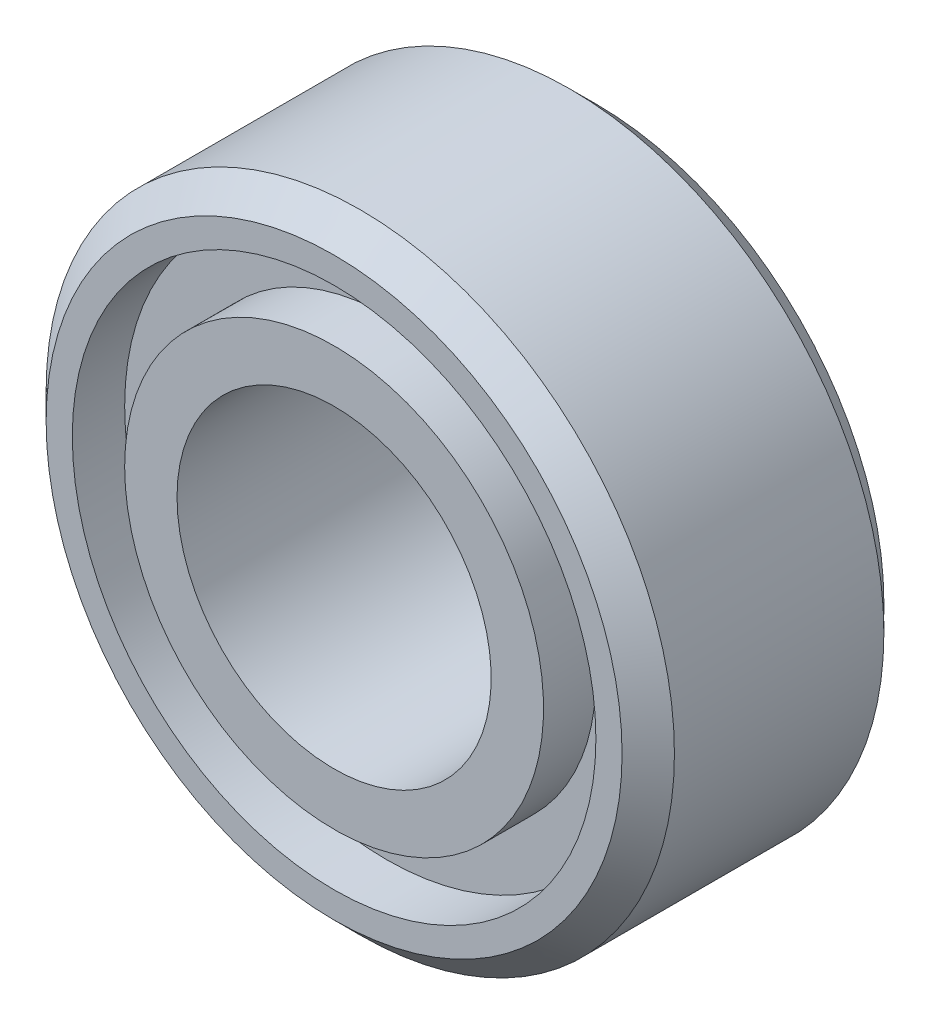
SolidWorks part; units mm, degrees
ref_plane "Front Plane" through (0, 0, 0) normal (0, 0, 1) x (1, 0, 0)
ref_plane "Top Plane" through (0, 0, 0) normal (0, 1, 0) x (1, 0, 0)
ref_plane "Right Plane" through (0, 0, 0) normal (1, 0, 0) x (0, 0, -1)
ref_plane "Plane1" through (0, 0, 0) normal (0, -1, 0) x (1, 0, 0)
sketch "Sketch1" plane through (0, 0, 0) normal (0, -1, 0) x (1, 0, 0)
  line L0 (3, -0.25) -> (2.75, 0)
  line L1 (2.75, 0) -> (2.5, 0)
  line L2 (2.5, 0) -> (2.5, -0.5)
  line L3 (2.5, -0.5) -> (2, -0.5)
  line L4 (2, -0.5) -> (2, 0)
  line L5 (2, 0) -> (1.5, 0)
  line L6 (1.5, 0) -> (1.5, -2.5)
  line L7 (1.5, -2.5) -> (2, -2.5)
  line L8 (2, -2.5) -> (2, -2)
  line L9 (2, -2) -> (2.5, -2)
  line L10 (2.5, -2) -> (2.5, -2.5)
  line L11 (2.5, -2.5) -> (2.75, -2.5)
  line L12 (2.75, -2.5) -> (3, -2.25)
  line L13 (3, -2.25) -> (3, -0.25)
  line L14 (0, 2.5) -> (0, -2.5) construction
  dimension "D1" = 3
  dimension "D2" = 0.25
  dimension "D3" = 4
  dimension "D4" = 2.5
  dimension "D5" = 6
  dimension "D7" = 0.5
  dimension "D8" = 45
  dimension "D9" = 5
revolve "Revolve1" add sketch "Sketch1" angle 360 about L14 reverse direction yes
